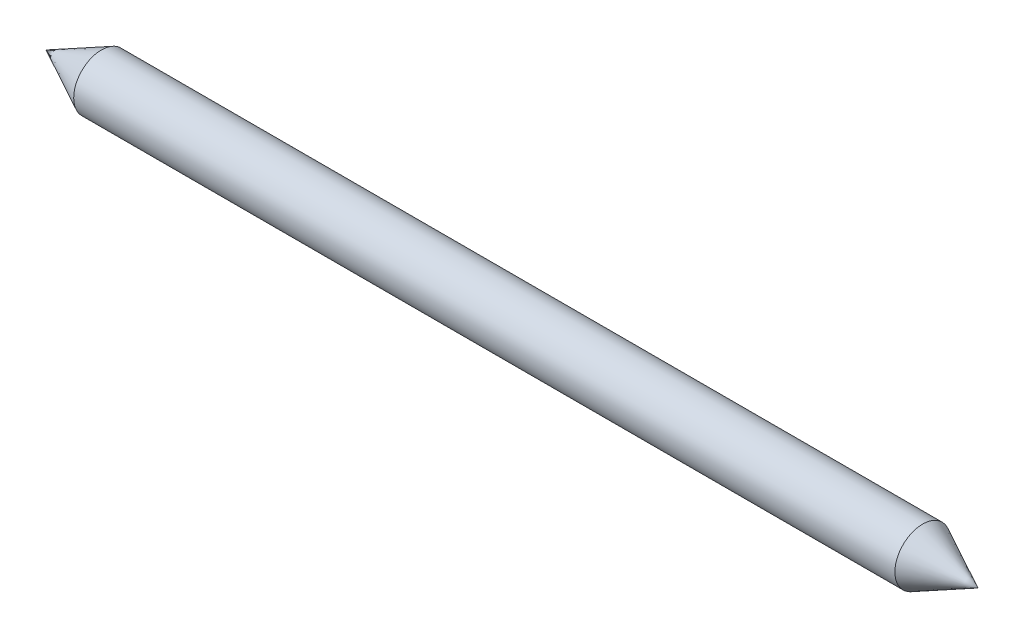
SolidWorks part; units mm, degrees
ref_plane "Front Plane" through (0, 0, 0) normal (0, 0, 1) x (1, 0, 0)
ref_plane "Top Plane" through (0, 0, 0) normal (0, 1, 0) x (1, 0, 0)
ref_plane "Right Plane" through (0, 0, 0) normal (1, 0, 0) x (0, 0, -1)
sketch "Sketch1" plane through (0, 0, 0) normal (0, 1, 0) x (1, 0, 0)
  line L0 (-213.6775, 0) -> (213.6775, 0)
  line L1 (213.6775, 0) -> (188.2775, 12.7)
  line L2 (188.2775, 12.7) -> (-188.2775, 12.7)
  line L3 (-188.2775, 12.7) -> (-213.6775, 0)
  point P5 (0, 0)
  dimension "D1" = 427.355
  dimension "D2" = 12.7
  dimension "D3" = 25.4
revolve "Revolve1" add sketch "Sketch1" angle 360 about L0
